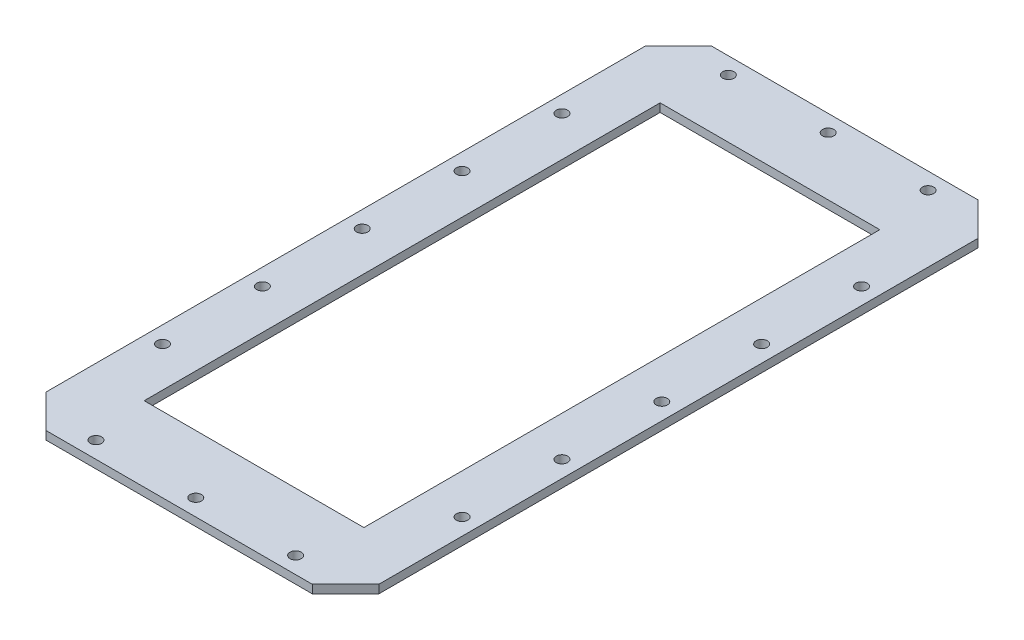
SolidWorks part; units mm, degrees
ref_plane "Front Plane" through (0, 0, 0) normal (0, 0, 1) x (1, 0, 0)
ref_plane "Top Plane" through (0, 0, 0) normal (0, 1, 0) x (1, 0, 0)
ref_plane "Right Plane" through (0, 0, 0) normal (1, 0, 0) x (0, 0, -1)
sketch "Sketch2" plane through (0, 0, 0) normal (0, 1, 0) x (1, 0, 0)
  line L0 (0, 12.7) -> (0, 241.3)
  line L1 (12.7, 254) -> (114.3, 254)
  line L2 (127, 241.3) -> (127, 12.7)
  line L3 (114.3, 0) -> (12.7, 0)
  line L4 (0, 241.3) -> (12.7, 254)
  line L5 (114.3, 254) -> (127, 241.3)
  line L6 (127, 12.7) -> (114.3, 0)
  line L7 (12.7, 0) -> (0, 12.7)
  line L8 (63.5, 254) -> (63.5, -20.3774) construction
  line L10 (0, 127) -> (136.1553, 127) construction
  line L11 (21.59, 225.425) -> (105.41, 225.425)
  line L12 (21.59, 225.425) -> (21.59, 28.575)
  line L13 (21.59, 28.575) -> (105.41, 28.575)
  line L14 (105.41, 225.425) -> (105.41, 28.575)
  line L17 (21.59, 225.425) -> (105.41, 28.575) construction
  line L18 (21.59, 28.575) -> (105.41, 225.425) construction
  circle A1 centre (6.35, 165.1) radius 2.159
  circle A13 centre (25.4, 247.65) radius 2.159
  circle A42 centre (6.35, 203.2) radius 2.159
  circle A43 centre (63.5, 247.65) radius 2.159
  circle A46 centre (6.35, 127) radius 2.159
  circle A56 centre (120.65, 127) radius 2.159
  circle A57 centre (120.65, 165.1) radius 2.159
  circle A58 centre (120.65, 203.2) radius 2.159
  circle A59 centre (101.6, 247.65) radius 2.159
  circle A60 centre (101.6, 6.35) radius 2.159
  circle A61 centre (63.5, 6.35) radius 2.159
  circle A62 centre (25.4, 6.35) radius 2.159
  circle A63 centre (120.65, 50.8) radius 2.159
  circle A64 centre (6.35, 50.8) radius 2.159
  circle A65 centre (120.65, 88.9) radius 2.159
  circle A66 centre (6.35, 88.9) radius 2.159
  point P0 (63.5, 127)
  point P37 (127, 127)
  point P42 (63.5, 0)
  dimension "D8" = 28.575
  dimension "D9" = 21.59
  dimension "D14" = 101.6
  dimension "D16" = 12.7
  dimension "D17" = 254
  dimension "D22" = 228.6
  dimension "D24" = 38.1
  dimension "D30" = 38.1
  dimension "D32" = 4.318
  dimension "D33" = 4.318
  dimension "D36" = 101.6
  dimension "D37" = 228.6
  dimension "D44" = 4.318
  dimension "D45" = 6.35
  dimension "D49" = 4.318
  dimension "D50" = 4.318
  dimension "D51" = 6.35
  dimension "D7" = 127
  dimension "D15" = 12.7
  dimension "D67" = 38.1
extrude "Boss-Extrude1" add sketch "Sketch2" along normal blind 3.175 contours L7 L3 L6 L2 L5 L1 L4 L0 A46 A66 A43 A42 A64 A13 A59 A56 region at (2.8398, 0, -127)
